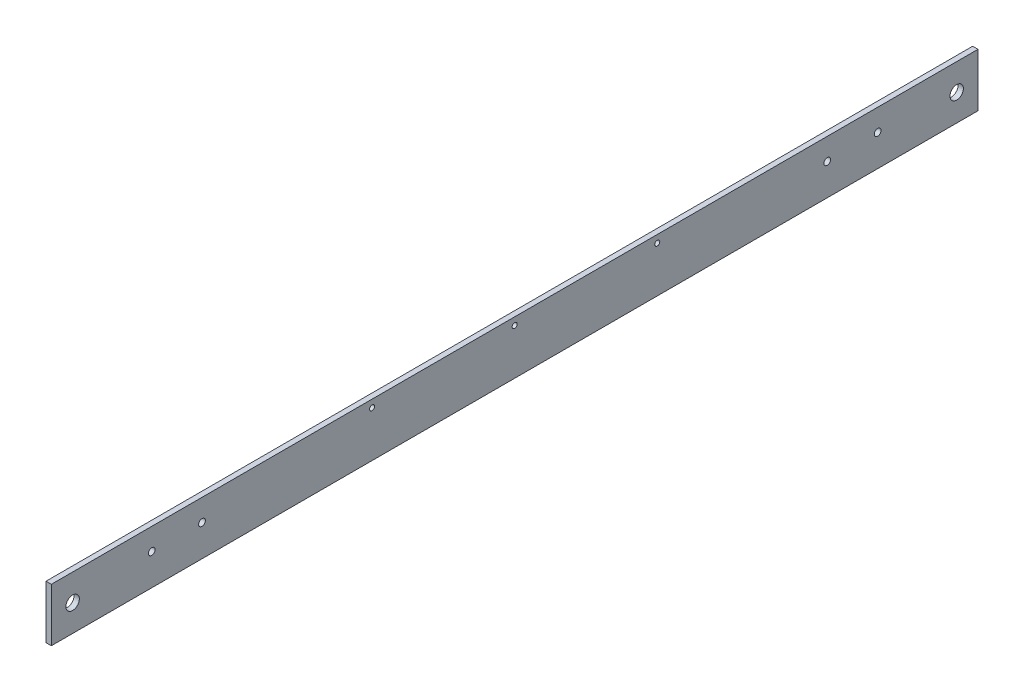
SolidWorks part; units mm, degrees
ref_plane "Front Plane" through (0, 0, 0) normal (0, 0, 1) x (1, 0, 0)
ref_plane "Top Plane" through (0, 0, 0) normal (0, 1, 0) x (1, 0, 0)
ref_plane "Right Plane" through (0, 0, 0) normal (1, 0, 0) x (0, 0, -1)
sketch "Sketch1" plane through (0, 0, 0) normal (1, 0, 0) x (0, 0, -1)
  line L1 (0, 0) -> (552.45, 0)
  line L2 (0, 0) -> (0, 31.75)
  line L3 (0, 31.75) -> (552.45, 31.75)
  line L4 (552.45, 0) -> (552.45, 31.75)
  circle A0 centre (12.7, 15.875) radius 4
  circle A1 centre (539.75, 15.875) radius 4
  circle A2 centre (462.625, 18.75) radius 2
  circle A3 centre (492.625, 18.75) radius 2
  circle A4 centre (59.825, 18.75) radius 2
  circle A5 centre (89.825, 18.75) radius 2
  dimension "D9" = 4
  dimension "D1" = 31.75
  dimension "D2" = 552.45
  dimension "D4" = 15.875
  dimension "D5" = 12.7
  dimension "D6" = 12.7
  dimension "D7" = 539.75
  dimension "D8" = 30
  dimension "D10" = 13
  dimension "D11" = 59.825
  dimension "D12" = 462.625
  dimension "D13" = 492.625
  dimension "D14" = 59.825
  dimension "D15" = 30
extrude "Boss-Extrude2" add sketch "Sketch1" along normal blind 3.175
sketch "Sketch2" plane through (3.175, 0, 0) normal (1, 0, 0) x (0, 0, -1)
  line L0 (0, 31.75) -> (0, 0) construction
  line L1 (552.45, 0) -> (552.45, 31.75) construction
  line L2 (552.45, 31.75) -> (0, 31.75) construction
  circle A0 centre (191.225, 27.25) radius 1.5
  circle A1 centre (276.225, 27.25) radius 1.5
  circle A2 centre (361.225, 27.25) radius 1.5
  dimension "D6" = 3
  dimension "D1" = 170
  dimension "D2" = 191.225
  dimension "D3" = 85
  dimension "D4" = 191.225
  dimension "D5" = 4.5
extrude "LightGuideMountHolesCut-Extrude1" cut sketch "Sketch2" against normal through all
equation "\"RailThickness\"= .125in'Spec"
equation "\"VSWidth\"= 1.25in'Spec"
equation "\"SideRailLength\"= 21.75in"
equation "\"StepperHolePadSize\"= \"StepperHoleDiameter\""
equation "\"D1@Sketch1\"=\"TopRailHeight\""
equation "\"D2@Sketch1\"=\"SideRailLength\""
equation "\"FrameFastenerHoleDiameter\"= 8mm"
equation "\"D3@Sketch1\"=\"FrameFastenerHoleDiameter\""
equation "\"D4@Sketch1\"=\"TopRailHeight\"/2"
equation "\"D5@Sketch1\"=\"FrameFastenerHoleOffsetFromEdge\""
equation "\"D6@Sketch1\"=\"FrameFastenerHoleOffsetFromEdge\""
equation "\"D1@Boss-Extrude2\"=\"RailThickness\""
equation "\"FrameFastenerHoleOffsetFromEdge\"= \"VSWidth\" / 2 - \"GapBetweenVerticalSupportsAndRails\" / 2"
equation "\"TopRailHeight\"= 1.25in"
equation "\"GapBetweenVerticalSupportsAndRails\"= \"RailThickness\" * 2"
equation "\"AngleBracketSmallHoleDiameter\"= 4mm"
equation "\"AngleBracketSlotDistanceBetweenHoles\"= 30mm"
equation "\"AngleBracketSlotDistanceFromTop\"= 13mm"
equation "\"D8@Sketch1\"=\"AngleBracketSlotDistanceBetweenHoles\""
equation "\"D9@Sketch1\"=\"AngleBracketSmallHoleDiameter\""
equation "\"D10@Sketch1\"=\"AngleBracketSlotDistanceFromTop\""
equation "\"AngleBracketSlotDistanceFromCorner\"= \"AngleBracketSlotDistanceFromBack\" - \"GapBetweenVerticalSupportsAndRails\" / 2'Equals 61.825"
equation "\"D11@Sketch1\"= \"AngleBracketSlotDistanceFromCorner\" - 2mm 'Minus 2mm to get screw hole in middle of slot"
equation "\"AngleBracketSlotDistanceFromBack\"= 65mm"
equation "\"D14@Sketch1\"= \"AngleBracketSlotDistanceFromCorner\" - 2mm'Minus 2mm to get screw hole in middle of slot"
equation "\"D15@Sketch1\"=\"AngleBracketSlotDistanceBetweenHoles\""
equation "\"D2@Sketch2\"= ( \"SideRailLength\" - \"LightStripLength\" + \"LightStripGuideMountingHoleFromLeftOrRightSide\" * 2 ) / 2"
equation "\"LightStripLength\"= 270mm'Spec"
equation "\"LightStripGuideMountingHoleFromLeftOrRightSide\"= 50mm"
equation "\"D3@Sketch2\"=(\"LightStripLength\" - \"LightStripGuideMountingHoleFromLeftOrRightSide\"*2)/2"
equation "\"D1@Sketch2\"=\"LightStripLength\" - \"LightStripGuideMountingHoleFromLeftOrRightSide\" * 2"
equation "\"M3HoleDiameter\"= 3mm"
equation "\"D6@Sketch2\"=\"M3HoleDiameter\""
equation "\"LightStripGuideMountingHoleFromTop\" = 4.5mm"
equation "\"D5@Sketch2\"=\"LightStripGuideMountingHoleFromTop\""
